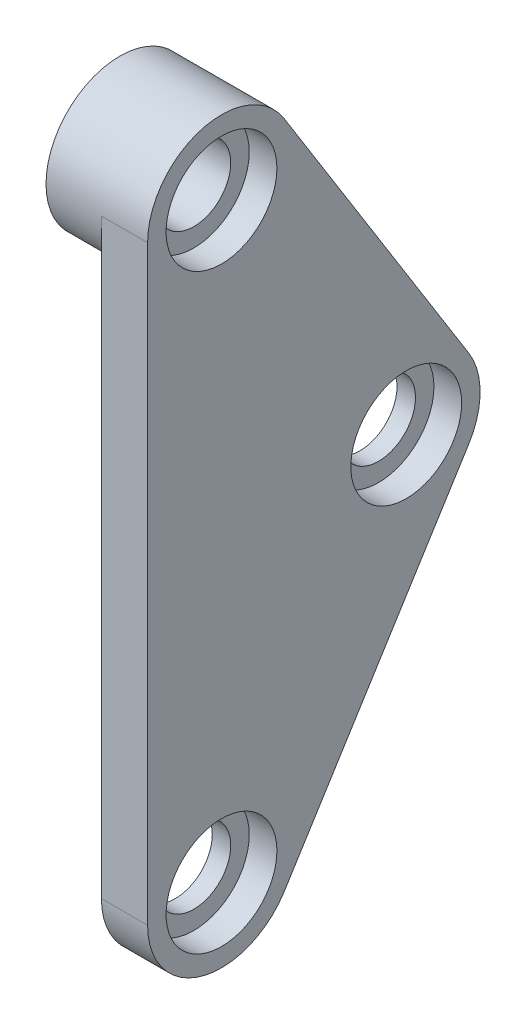
SolidWorks part; units mm, degrees
ref_plane "前视基准面" through (0, 0, 0) normal (0, 0, 1) x (1, 0, 0)
ref_plane "上视基准面" through (0, 0, 0) normal (0, 1, 0) x (1, 0, 0)
ref_plane "右视基准面" through (0, 0, 0) normal (1, 0, 0) x (0, 0, -1)
other "Configuration Table"
sketch "草图1" plane through (0, 0, 0) normal (1, 0, 0) x (0, 0, -1)
  line L0 (0, -20) -> (18, -20) construction
  line L1 (0, 0) -> (18, 0) construction
  line L2 (0, 0) -> (0, -40)
  line L3 (0, -40) -> (18, -40) construction
  line L4 (18, 0) -> (18, -40) construction
  line L5 (7.392, -1.88) -> (17.392, -17.88)
  line L6 (17.392, -22.12) -> (7.392, -38.12)
  circle A0 centre (4, -4) radius 4
  circle A1 centre (4, -36) radius 4
  circle A2 centre (14, -20) radius 4
  circle A3 centre (4, -4) radius 2
  circle A4 centre (14, -20) radius 2
  circle A5 centre (4, -36) radius 2
  dimension "D1" = 8
  dimension "D2" = 4
  dimension "D3" = 40
  dimension "D4" = 18
extrude "凸台-拉伸1" add sketch "草图1" along normal blind 2.5 contours A2 L5 A0 L2 A1 L6 | A0 | A2 | A1 region at (0, -20, -6.5849)
extrude "凸台-拉伸2" add sketch "草图1<4>" against normal blind 3 contours A0
sketch "草图1<4>" plane through (0, 0, 0) normal (1, 0, 0) x (0, 0, -1) same geometry as "草图1"
extrude "切除-拉伸1" cut sketch "草图1<3>" along normal through all both and the other way through all contours A3 | A4 | A5
sketch "草图1<3>" plane through (0, 0, 0) normal (1, 0, 0) x (0, 0, -1) same geometry as "草图1"
sketch "草图2" plane through (2.5, 0, 0) normal (1, 0, 0) x (0, 0, -1)
  circle A0 centre (4, -4) radius 3
  circle A1 centre (14, -20) radius 3
  circle A2 centre (4, -36) radius 3
  circle M3 centre (4, -4) radius 2
  circle M5 centre (4, -36) radius 2
  arc M9 (7.392, -1.88) -> (0, -4) centre (4, -4) ccw
  arc M11 (0, -36) -> (7.392, -38.12) centre (4, -36) ccw
  dimension "D1" = 6
extrude "切除-拉伸2" cut sketch "草图2" against normal blind 1.5 contours A0 M9 M3 | A2 M11 M5 | A1 region at (2.5, -4, -1.0849) region at (2.5, -36, -1.0849)
